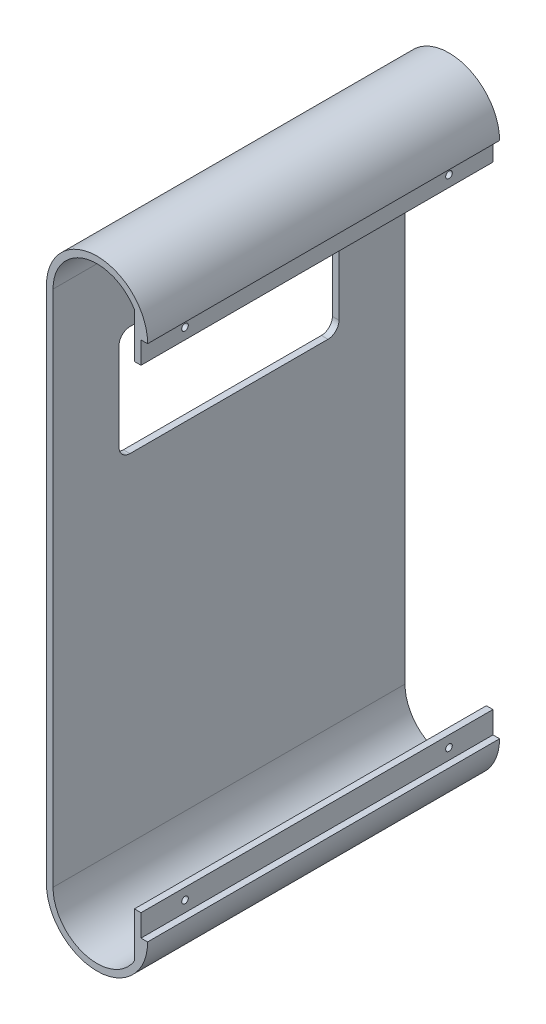
SolidWorks part; units mm, degrees
ref_plane "Front Plane" through (0, 0, 0) normal (0, 0, 1) x (1, 0, 0)
ref_plane "Top Plane" through (0, 0, 0) normal (0, 1, 0) x (1, 0, 0)
ref_plane "Right Plane" through (0, 0, 0) normal (1, 0, 0) x (0, 0, -1)
sketch "Sketch1" plane through (0, 0, 0) normal (0, 0, 1) x (1, 0, 0)
  line L0 (0, -75) -> (-40, -75) construction
  line L1 (33, 42.75) -> (-40, 42.75) construction
  line L3 (-40, -75) -> (-40, 160.5)
  line L4 (-43, -75) -> (-43, 160.5)
  line L5 (0, 160.5) -> (3, 160.5)
  line L6 (0, -75) -> (3, -75)
  arc A0 (-40, -75) -> (0, -75) centre (-20, -75) ccw
  arc A1 (-40, 160.5) -> (0, 160.5) centre (-20, 160.5) cw
  arc A2 (-43, 160.5) -> (3, 160.5) centre (-20, 160.5) cw
  arc A3 (-43, -75) -> (3, -75) centre (-20, -75) ccw
  dimension "D1" = 3
extrude "Boss-Extrude1" add sketch "Sketch1" against normal up to surface (160 mm away)
ref_plane "Plane1" through (3, 0, 0) normal (1, 0, 0) x (0, 0, -1)
sketch "Sketch5" plane through (0, 0, -160) normal (0, 0, -1) x (-1, 0, 0)
  line L0 (43, 42.75) -> (-4.5, 42.75) construction
  line L1 (3, -65) -> (0, -65)
  line L2 (3, -65) -> (3, -86.3578)
  line L3 (3, -86.3578) -> (0, -86.3578)
  line L4 (0, -65) -> (0, -86.3578)
  line L5 (43, 160.5) -> (43, -75) construction
  line L6 (0, 150.5) -> (0, 171.8578)
  line L7 (3, 171.8578) -> (0, 171.8578)
  line L8 (3, 150.5) -> (3, 171.8578)
  line L9 (3, 150.5) -> (0, 150.5)
  arc A0 (-3, -75) -> (43, -75) centre (20, -75) ccw construction
extrude "Boss-Extrude4" add sketch "Sketch5" against normal up to surface (160 mm away)
sketch "Sketch7" plane through (-3, 0, 0) normal (-1, 0, 0) x (0, 0, 1)
  line L0 (0, -65) -> (-160, -65) construction
  line L1 (0, -65) -> (-160, -65) construction
  line L2 (0, 150.5) -> (-160, 150.5) construction
  line L3 (0, 150.5) -> (-160, 150.5) construction
  line L4 (-160, 160.5) -> (-160, -75) construction
  line L5 (0, 160.5) -> (0, -75) construction
  line L6 (-160, 42.75) -> (0, 42.75) construction
  circle A0 centre (-140, -70) radius 1.5
  circle A1 centre (-20, -70) radius 1.5
  circle A2 centre (-20, 155.5) radius 1.5
  circle A3 centre (-140, 155.5) radius 1.5
  dimension "D1" = 5
  dimension "D2" = 20
  dimension "D4" = 5
  dimension "D3" = 20
extrude "Cut-Extrude2" cut sketch "Sketch7" against normal through all
sketch "Sketch8" plane through (-43, 0, 0) normal (-1, 0, 0) x (0, 0, 1)
  line L0 (-30, 123.2573) -> (-30, 83.2573) construction
  line L1 (-125, 128.2573) -> (-35, 128.2573)
  line L2 (-130, 123.2573) -> (-130, 83.2573)
  line L3 (-125, 78.2573) -> (-35, 78.2573)
  line L4 (-30, 123.2573) -> (-30, 83.2573)
  line L5 (-35, 78.2573) -> (-125, 78.2573) construction
  line L6 (-130, 83.2573) -> (-130, 123.2573) construction
  line L7 (-125, 128.2573) -> (-35, 128.2573) construction
  arc A0 (-125, 128.2573) -> (-130, 123.2573) centre (-125, 123.2573) ccw
  arc A1 (-130, 83.2573) -> (-125, 78.2573) centre (-125, 83.2573) ccw
  arc A2 (-35, 78.2573) -> (-30, 83.2573) centre (-35, 83.2573) ccw
  arc A3 (-35, 128.2573) -> (-30, 123.2573) centre (-35, 123.2573) cw
  dimension "D5" = 5
  dimension "D1" = 0
  dimension "D2" = 0
  dimension "D3" = 0
  dimension "D4" = 0
extrude "Cut-Extrude3" cut sketch "Sketch8" against normal up to surface (3 mm away)
